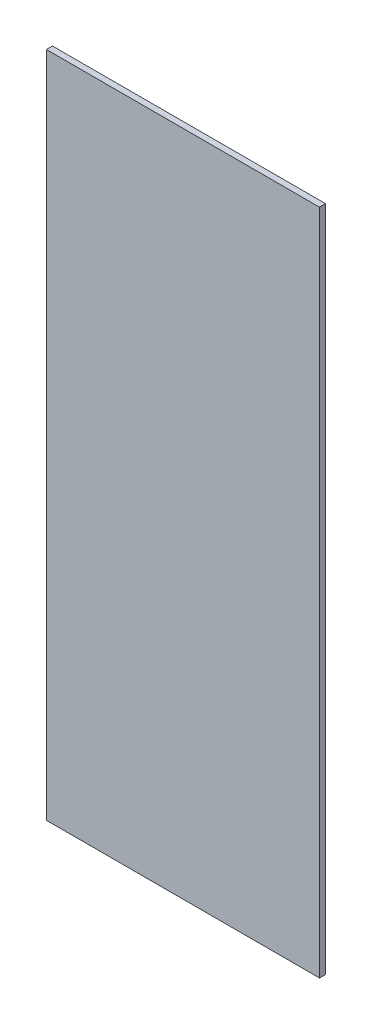
SolidWorks part; units mm, degrees
material "201 Annealed Stainless Steel (SS)"
ref_plane "Front Plane" through (0, 0, 0) normal (0, 0, 1) x (1, 0, 0)
ref_plane "Top Plane" through (0, 0, 0) normal (0, 1, 0) x (1, 0, 0)
ref_plane "Right Plane" through (0, 0, 0) normal (1, 0, 0) x (0, 0, -1)
sketch "Sketch1" plane through (0, 0, 0) normal (0, 0, 1) x (1, 0, 0)
  line L1 (-45, -110) -> (45, -110)
  line L2 (-45, -110) -> (-45, 110)
  line L3 (-45, 110) -> (45, 110)
  line L4 (45, -110) -> (45, 110)
  line L5 (-45, -110) -> (45, 110) construction
  line L6 (-45, 110) -> (45, -110) construction
  point P0 (0, 0)
  dimension "D1" = 90
  dimension "D2" = 220
extrude "Boss-Extrude1" add sketch "Sketch1" along normal blind 2
sketch "Sketch2" plane through (0, 0, 0) normal (0, 0, -1) x (-1, 0, 0)
  line L0 (61, 145) -> (61, -145) construction
  line L1 (-61, 314.7216) -> (-204.3993, 314.7216)
  line L2 (-61, 314.7216) -> (-61, -251.9618)
  line L3 (-61, -251.9618) -> (-204.3993, -251.9618)
  line L4 (-204.3993, 314.7216) -> (-204.3993, -251.9618)
  line L6 (61, 279.3211) -> (244.4765, 279.3211)
  line L7 (61, 279.3211) -> (61, -295.1839)
  line L8 (61, -295.1839) -> (244.4765, -295.1839)
  line L9 (244.4765, 279.3211) -> (244.4765, -295.1839)
  line L10 (-61, -145) -> (-61, 145) construction
  dimension "D1" = 122
extrude "Cut-Extrude1" [suppressed] cut sketch "Sketch2" against normal through all
sketch "Sketch3" [suppressed] plane through (49, 0, 0) normal (1, 0, 0) x (0, 0, -1)
  circle A0 centre (-6.722, 55.3681) radius 5.3835
surface "Surface-Extrude1" [suppressed] sketch "Sketch3"
sketch "Sketch4" [suppressed] plane through (-49, 0, 0) normal (-1, 0, 0) x (0, 0, 1)
  line L1 (2, 80) -> (0, 80) construction
  line L2 (0, -80) -> (0, 80) construction
  point P0 (7.5, 76)
  dimension "D1" = 4
  dimension "D2" = 7.5
ref_axis "Axis1" [suppressed] through (-49, 76, 7.5) along (1, 0, 0)
sketch "Sketch5" [suppressed] plane through (0, 0, 0) normal (0, 0, -1) x (-1, 0, 0)
  line L0 (49, 80) -> (49, -80) construction
  line L1 (-49, 80) -> (49, 80)
  line L2 (-49, 80) -> (-49, 60.2594)
  line L3 (-49, 60.2594) -> (49, 60.2594)
  line L4 (49, 80) -> (49, 60.2594)
extrude "Cut-Extrude2" [suppressed] cut sketch "Sketch5" against normal blind 3
sketch "Sketch6" [suppressed] plane through (0, 0, 2) normal (0, 0, 1) x (1, 0, 0)
  line L0 (0, 0) -> (103.2002, 0) construction
  line L1 (-40, 80) -> (-40, 108.3319) construction
  line L2 (-40, 80) -> (-27.987, 80) construction
  line L3 (0, 0) -> (0, 138.3235) construction
  line L4 (40, 80) -> (27.987, 80) construction
  line L5 (40, 80) -> (40, 108.3319) construction
  line L6 (40, -80) -> (40, -108.3319) construction
  line L7 (40, -80) -> (27.987, -80) construction
  line L8 (-40, -80) -> (-27.987, -80) construction
  line L9 (-40, -80) -> (-40, -108.3319) construction
  circle A0 centre (-40, 80) radius 4.5
  circle A2 centre (-45.8, 85.8) radius 1.95
  circle A3 centre (-45.8, 74.2) radius 1.95
  circle A4 centre (-34.2, 74.2) radius 1.95
  circle A5 centre (-34.2, 85.8) radius 1.95
  circle A6 centre (34.2, 85.8) radius 1.95
  circle A7 centre (34.2, 74.2) radius 1.95
  circle A8 centre (45.8, 74.2) radius 1.95
  circle A9 centre (45.8, 85.8) radius 1.95
  circle A10 centre (40, 80) radius 4.5
  circle A11 centre (40, -80) radius 4.5
  circle A12 centre (45.8, -85.8) radius 1.95
  circle A13 centre (45.8, -74.2) radius 1.95
  circle A14 centre (34.2, -74.2) radius 1.95
  circle A15 centre (34.2, -85.8) radius 1.95
  circle A16 centre (-34.2, -85.8) radius 1.95
  circle A17 centre (-34.2, -74.2) radius 1.95
  circle A18 centre (-45.8, -74.2) radius 1.95
  circle A19 centre (-45.8, -85.8) radius 1.95
  circle A20 centre (-40, -80) radius 4.5
  circle A21 centre (-40, 80) radius 5.1 construction
  dimension "D1" = 9
  dimension "D3" = 3.9
extrude "Leandut_holes" [suppressed] cut sketch "Sketch6" against normal through all
chamfer "Chamfer1" [suppressed] distance 5 angle 45
sketch "Sketch7" [suppressed] plane through (0, 0, 2) normal (0, 0, 1) x (1, 0, 0)
  line L0 (106, 145) -> (-106, 145) construction
  line L1 (-56, -110) -> (56, -110)
  line L2 (-56, -110) -> (-56, 125)
  line L3 (-56, 125) -> (56, 125)
  line L4 (56, -110) -> (56, 125)
  line L5 (0, 0) -> (0, -66.8576) construction
  line L7 (-106, 145) -> (-106, -145) construction
  point P0 (0, 0)
  dimension "D1" = 20
  dimension "D2" = 50
  dimension "D3" = 112
  dimension "D4" = 125
extrude "Plunger-Window" [suppressed] cut sketch "Sketch7" against normal through all
sketch "Sketch8" [suppressed] plane through (0, 0, 2) normal (0, 0, 1) x (1, 0, 0)
  line L0 (106, 145) -> (56, 145) construction
  line L1 (-56, 125) -> (56, 125)
  line L2 (-56, 125) -> (-56, 145)
  line L3 (-56, 145) -> (56, 145)
  line L4 (56, 125) -> (56, 145)
  line L5 (56, -110) -> (56, 125) construction
extrude "Cut-Extrude3" [suppressed] cut sketch "Sketch8" against normal blind 5
